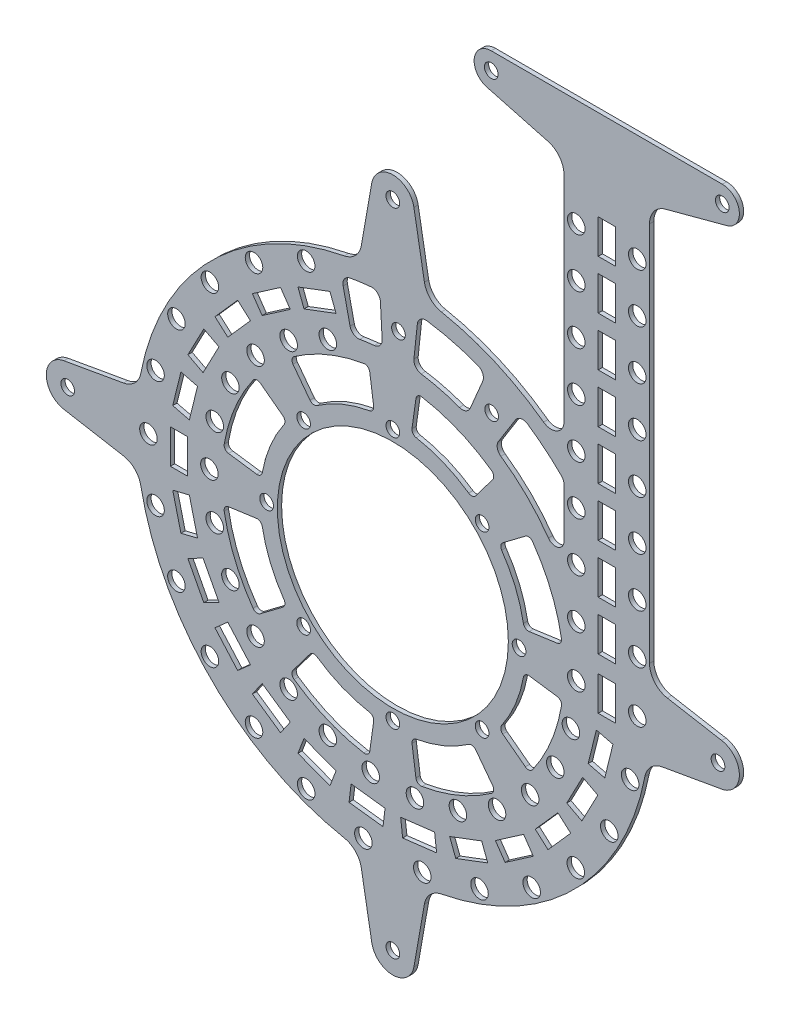
SolidWorks part; units mm, degrees
material "Thornel Mat VMA"
ref_plane "前视基准面" through (0, 0, 0) normal (0, 0, 1) x (1, 0, 0)
ref_plane "上视基准面" through (0, 0, 0) normal (0, 1, 0) x (1, 0, 0)
ref_plane "右视基准面" through (0, 0, 0) normal (1, 0, 0) x (0, 0, -1)
sketch "草图1" plane through (0, 0, 0) normal (0, 0, 1) x (1, 0, 0)
  line L1 (-100, -150) -> (100, -150)
  line L2 (-100, -150) -> (-100, 150)
  line L3 (-100, 150) -> (100, 150)
  line L4 (100, -150) -> (100, 150)
  line L5 (0, 150) -> (0, -150) construction
  line L6 (-100, 0) -> (100, 0) construction
  point P0 (0, 0)
  dimension "D1" = 200
  dimension "D2" = 300
extrude "凸台-拉伸1" add sketch "草图1" along normal blind 1
sketch "草图2" plane through (0, 0, 1) normal (0, 0, 1) x (1, 0, 0)
  line L13 (40, 101.0647) -> (40, 50.9902)
  line L14 (21.9647, 109.7339) -> (36.2941, 105.8944)
  line L15 (77, 117.5976) -> (23, 117.5976)
  line L16 (63.7059, 105.8944) -> (78.0353, 109.7339)
  line L17 (60, 12.0939) -> (60, 101.0647)
  line L18 (76.8682, 4.924) -> (64.1318, 7.1698)
  line L19 (62.9572, -7.3769) -> (76.8682, -4.924)
  line L20 (4.924, -76.8682) -> (7.3769, -62.9572)
  line L21 (-7.3769, -62.9572) -> (-4.924, -76.8682)
  line L22 (-76.8682, -4.924) -> (-62.9572, -7.3769)
  line L23 (-62.9572, 7.3769) -> (-76.8682, 4.924)
  line L24 (-4.924, 76.8682) -> (-7.3769, 62.9572)
  line L25 (7.3769, 62.9572) -> (4.924, 76.8682)
  line L26 (40, 101.0647) -> (40, 50.9902)
  line L27 (21.9647, 109.7339) -> (36.2941, 105.8944)
  line L28 (77, 117.5976) -> (23, 117.5976)
  line L29 (63.7059, 105.8944) -> (78.0353, 109.7339)
  line L30 (60, 12.0939) -> (60, 101.0647)
  line L31 (76.8682, 4.924) -> (64.1318, 7.1698)
  line L32 (62.9572, -7.3769) -> (76.8682, -4.924)
  line L33 (4.924, -76.8682) -> (7.3769, -62.9572)
  line L34 (-7.3769, -62.9572) -> (-4.924, -76.8682)
  line L35 (-76.8682, -4.924) -> (-62.9572, -7.3769)
  line L36 (-62.9572, 7.3769) -> (-76.8682, 4.924)
  line L37 (-4.924, 76.8682) -> (-7.3769, 62.9572)
  line L38 (7.3769, 62.9572) -> (4.924, 76.8682)
  arc A20 (40, 101.0647) -> (36.2941, 105.8944) centre (35, 101.0647) ccw
  arc A21 (23, 117.5976) -> (21.9647, 109.7339) centre (23, 113.5976) ccw
  arc A22 (78.0353, 109.7339) -> (77, 117.5976) centre (77, 113.5976) ccw
  arc A23 (63.7059, 105.8944) -> (60, 101.0647) centre (65, 101.0647) ccw
  arc A24 (60, 12.0939) -> (64.1318, 7.1698) centre (65, 12.0939) ccw
  arc A25 (76.8682, -4.924) -> (76.8682, 4.924) centre (76, 0) ccw
  arc A26 (62.9572, -7.3769) -> (58.9158, -11.3547) centre (63.8254, -12.301) ccw
  arc A27 (11.3547, -58.9158) -> (58.9158, -11.3547) centre (0, 0) ccw
  arc A28 (11.3547, -58.9158) -> (7.3769, -62.9572) centre (12.301, -63.8254) ccw
  arc A29 (-4.924, -76.8682) -> (4.924, -76.8682) centre (0, -76) ccw
  arc A30 (-7.3769, -62.9572) -> (-11.3547, -58.9158) centre (-12.301, -63.8254) ccw
  arc A31 (-58.9158, -11.3547) -> (-11.3547, -58.9158) centre (0, 0) ccw
  arc A32 (-58.9158, -11.3547) -> (-62.9572, -7.3769) centre (-63.8254, -12.301) ccw
  arc A33 (-76.8682, 4.924) -> (-76.8682, -4.924) centre (-76, 0) ccw
  arc A34 (-62.9572, 7.3769) -> (-58.9158, 11.3547) centre (-63.8254, 12.301) ccw
  arc A35 (-11.3547, 58.9158) -> (-58.9158, 11.3547) centre (0, 0) ccw
  arc A36 (-11.3547, 58.9158) -> (-7.3769, 62.9572) centre (-12.301, 63.8254) ccw
  arc A37 (4.924, 76.8682) -> (-4.924, 76.8682) centre (0, 76) ccw
  arc A38 (7.3769, 62.9572) -> (11.3547, 58.9158) centre (12.301, 63.8254) ccw
  arc A39 (35.2381, 48.5621) -> (11.3547, 58.9158) centre (0, 0) ccw
  arc A40 (40, 101.0647) -> (36.2941, 105.8944) centre (35, 101.0647) ccw
  arc A41 (23, 117.5976) -> (21.9647, 109.7339) centre (23, 113.5976) ccw
  arc A42 (78.0353, 109.7339) -> (77, 117.5976) centre (77, 113.5976) ccw
  arc A43 (63.7059, 105.8944) -> (60, 101.0647) centre (65, 101.0647) ccw
  arc A44 (60, 12.0939) -> (64.1318, 7.1698) centre (65, 12.0939) ccw
  arc A45 (76.8682, -4.924) -> (76.8682, 4.924) centre (76, 0) ccw
  arc A46 (62.9572, -7.3769) -> (58.9158, -11.3547) centre (63.8254, -12.301) ccw
  arc A47 (11.3547, -58.9158) -> (58.9158, -11.3547) centre (0, 0) ccw
  arc A48 (11.3547, -58.9158) -> (7.3769, -62.9572) centre (12.301, -63.8254) ccw
  arc A49 (-4.924, -76.8682) -> (4.924, -76.8682) centre (0, -76) ccw
  arc A50 (-7.3769, -62.9572) -> (-11.3547, -58.9158) centre (-12.301, -63.8254) ccw
  arc A51 (-58.9158, -11.3547) -> (-11.3547, -58.9158) centre (0, 0) ccw
  arc A52 (-58.9158, -11.3547) -> (-62.9572, -7.3769) centre (-63.8254, -12.301) ccw
  arc A53 (-76.8682, 4.924) -> (-76.8682, -4.924) centre (-76, 0) ccw
  arc A54 (-62.9572, 7.3769) -> (-58.9158, 11.3547) centre (-63.8254, 12.301) ccw
  arc A55 (-11.3547, 58.9158) -> (-58.9158, 11.3547) centre (0, 0) ccw
  arc A56 (-11.3547, 58.9158) -> (-7.3769, 62.9572) centre (-12.301, 63.8254) ccw
  arc A57 (4.924, 76.8682) -> (-4.924, 76.8682) centre (0, 76) ccw
  arc A58 (7.3769, 62.9572) -> (11.3547, 58.9158) centre (12.301, 63.8254) ccw
  arc A59 (35.2381, 48.5621) -> (11.3547, 58.9158) centre (0, 0) ccw
  arc A82 (35.2381, 48.5621) -> (40, 50.9902) centre (37, 50.9902) ccw
  arc A83 (35.2381, 48.5621) -> (40, 50.9902) centre (37, 50.9902) ccw
  dimension "D1" = 0
extrude "切除-拉伸1" cut sketch "草图2" against normal blind 10 flip side to cut
sketch "草图3" plane through (0, 0, 1) normal (0, 0, 1) x (1, 0, 0)
  circle A0 centre (0, 0) radius 27
  dimension "D1" = 54
extrude "切除-拉伸2" cut sketch "草图3" against normal blind 10
sketch "草图4" plane through (0, 0, 1) normal (0, 0, 1) x (1, 0, 0)
  circle A0 centre (76, 0) radius 1.6
  circle A1 centre (0, 76) radius 1.6
  circle A2 centre (-76, 0) radius 1.6
  circle A3 centre (0, -76) radius 1.6
  circle A4 centre (77, 113.5976) radius 1.6
  circle A5 centre (23, 113.5976) radius 1.6
  dimension "D1" = 3.2
extrude "切除-拉伸3" cut sketch "草图4" against normal blind 10
sketch "草图5" plane through (0, 0, 0) normal (0, 0, -1) x (-1, 0, 0)
  line L2 (30.9722, 23.3393) -> (25.6982, 19.365)
  line L3 (31.8645, 4.4783) -> (38.404, 5.3973)
  circle A0 centre (0, 0) radius 29.5 construction
  circle A1 centre (0, 0) radius 27 construction
  circle A7 centre (29.5, 0) radius 1.6
  arc A8 (30.5162, 5.4554) -> (25.4358, 17.7207) centre (0, 0) ccw
  arc A9 (25.6982, 19.365) -> (25.4358, 17.7207) centre (26.4204, 18.4066) ccw
  arc A10 (32.6747, 23.0731) -> (30.9722, 23.3393) centre (31.6944, 22.3809) ccw
  arc A11 (39.4196, 6.7893) -> (32.6747, 23.0731) centre (0, 0) ccw
  arc A12 (38.404, 5.3973) -> (39.4196, 6.7893) centre (38.237, 6.5857) ccw
  arc A13 (30.5162, 5.4554) -> (31.8645, 4.4783) centre (31.6975, 5.6666) ccw
  dimension "D1" = 2.5
  dimension "D2" = 3.2
extrude "切除-拉伸4" cut sketch "草图5" against normal blind 10
pattern_circular "阵列(圆周)1" count 8 over 360 about axis through (0, 0, 0) along (0, 0, -1) of "切除-拉伸4"
sketch "草图6" plane through (0, 0, 1) normal (0, 0, 1) x (1, 0, 0)
  line L2 (-48, -4) -> (-52, -4)
  line L3 (-52, 4) -> (-48, 4)
  line L4 (-52, 4) -> (-52, -4)
  line L5 (-48, 4) -> (-48, -4)
  dimension "D1" = 4
  dimension "D2" = 48
  dimension "D3" = 4
extrude "切除-拉伸5" cut sketch "草图6" against normal blind 10
pattern_circular "阵列(圆周)2" count 26 over 360 about axis through (0, 0, 0) along (0, 0, -1) skipping 10, 11, 12 of "切除-拉伸5"
sketch "草图7" plane through (0, 0, 1) normal (0, 0, 1) x (1, 0, 0)
  line L2 (48, 16) -> (52, 16)
  line L3 (52, 8) -> (48, 8)
  line L4 (48, 16) -> (48, 8)
  line L5 (52, 16) -> (52, 8)
  line L6 (48, 4) -> (48, -4) construction
  dimension "D1" = 8
  dimension "D3" = 4
  dimension "D4" = 8
extrude "切除-拉伸6" cut sketch "草图7" against normal blind 10
pattern_linear "阵列(线性)1" count 8 spacing 11.5 along (0, 1, 0) of "切除-拉伸6"
sketch "草图8" plane through (0, 0, 1) normal (0, 0, 1) x (1, 0, 0)
  line L0 (0, 60) -> (0, 0) construction
  line L1 (-9.6769, 38.8118) -> (-14.5153, 58.2177)
  line L2 (26.2424, 30.1884) -> (39.3635, 45.2826)
  arc A0 (26.2424, 30.1884) -> (-9.6769, 38.8118) centre (0, 0) ccw
  arc A1 (39.3635, 45.2826) -> (-14.5153, 58.2177) centre (0, 0) ccw
  dimension "D1" = 80
  dimension "D2" = 120
  dimension "D3" = 14
  dimension "D4" = 41
extrude "凸台-拉伸2" add sketch "草图8" against normal up to surface (1 mm away) up to face at (50, 23.5, 0)
sketch "草图9" plane through (0, 0, 1) normal (0, 0, 1) x (1, 0, 0)
  line L0 (57.125, 0) -> (50, 0) construction
  line L1 (50, 4) -> (50, 0) construction
  line L2 (52, 4) -> (48, 4) construction
  circle A0 centre (57.125, 0) radius 2.05
  circle A1 centre (42.875, 0) radius 2.05
  dimension "D2" = 4.1
  dimension "D1" = 7.125
extrude "切除-拉伸7" cut sketch "草图9" against normal blind 10
pattern_circular "阵列(圆周)3" count 26 over 360 about axis through (0, 0, 1) along (0, 0, 1) skipping 1, 2, 3, 4, 5, 6, 7 of "切除-拉伸7"
sketch "草图10" plane through (0, 0, 1) normal (0, 0, 1) x (1, 0, 0)
  line L0 (42.875, 12) -> (57.125, 12) construction
  line L1 (50, 16) -> (50, 12) construction
  line L2 (52, 16) -> (48, 16) construction
  circle A0 centre (57.125, 12) radius 2.05
  circle A1 centre (42.875, 12) radius 2.05
  circle A2 centre (57.125, 0) radius 2.05 construction
  point P3 (50, 12)
  dimension "D1" = 4
  dimension "D2" = 14.25
extrude "切除-拉伸8" cut sketch "草图10" against normal blind 10
pattern_linear "阵列(线性)2" count 8 spacing 11.5 along (0, 1, 0) of "切除-拉伸8"
sketch "草图11" plane through (0, 0, 1) normal (0, 0, 1) x (1, 0, 0)
  circle A0 centre (23.0874, 44.3505) radius 1.6 construction
  circle A1 centre (1.3088, 49.9829) radius 1.6 construction
  circle A2 centre (23.0874, 44.3505) radius 1.6
  circle A3 centre (1.3088, 49.9829) radius 1.6
extrude "切除-拉伸9" cut sketch "草图11" against normal blind 10
sketch "草图12" plane through (0, 0, 0) normal (0, 0, -1) x (-1, 0, 0)
  line L4 (-40, 39.1918) -> (-40, 19.5)
  line L5 (-23.6397, 37.7016) -> (-29.7489, 47.4448)
  line L8 (3.0173, 55.9187) -> (2.3976, 44.4354)
  line L9 (9.582, 43.4561) -> (12.0583, 54.6864)
  line L12 (-21.8012, 51.582) -> (-17.3242, 40.9893)
  line L13 (-4.7199, 44.249) -> (-5.9397, 55.6841)
  arc A4 (-23.6397, 37.7016) -> (-40, 19.5) centre (0, 0) ccw
  arc A5 (-29.7489, 47.4448) -> (-40, 39.1918) centre (0, 0) ccw
  arc A8 (12.0583, 54.6864) -> (3.0173, 55.9187) centre (0, 0) ccw
  arc A9 (9.582, 43.4561) -> (2.3976, 44.4354) centre (0, 0) ccw
  arc A12 (-5.9397, 55.6841) -> (-21.8012, 51.582) centre (0, 0) ccw
  arc A13 (-4.7199, 44.249) -> (-17.3242, 40.9893) centre (0, 0) ccw
extrude "切除-拉伸10" cut sketch "草图12" against normal blind 10
fillet "圆角1" radius 2 12 edges at (-12.0583, 54.6864, 0.5) (-9.582, 43.4561, 0.5) (-2.3976, 44.4354, 0.5) (-3.0173, 55.9187, 0.5) (5.9397, 55.6841, 0.5) (4.7199, 44.249, 0.5) (17.3242, 40.9893, 0.5) (21.8012, 51.582, 0.5) (40, 19.5, 0.5) (40, 39.1918, 0.5) (29.7489, 47.4448, 0.5) (23.6397, 37.7016, 0.5)
